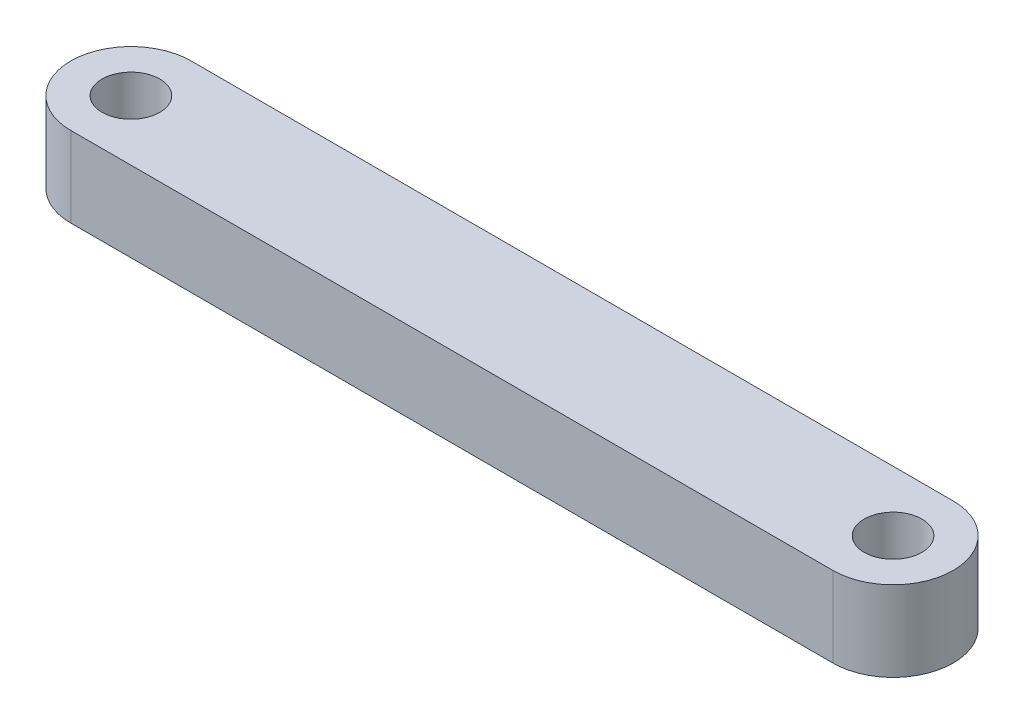
SolidWorks part; units mm, degrees
ref_plane "Front Plane" through (0, 0, 0) normal (0, 0, 1) x (1, 0, 0)
ref_plane "Top Plane" through (0, 0, 0) normal (0, 1, 0) x (1, 0, 0)
ref_plane "Right Plane" through (0, 0, 0) normal (1, 0, 0) x (0, 0, -1)
sketch "Sketch1" plane through (0, 0, 0) normal (0, 1, 0) x (1, 0, 0)
  line L0 (0, 0) -> (-60.325, 0) construction
  line L1 (0, -4.7625) -> (-60.325, -4.7625)
  line L2 (0, 4.7625) -> (-60.325, 4.7625)
  arc A0 (0, -4.7625) -> (0, 4.7625) centre (0, 0) ccw
  arc A1 (-60.325, 4.7625) -> (-60.325, -4.7625) centre (-60.325, 0) ccw
  circle A2 centre (-60.325, 0) radius 2.286
  circle A3 centre (0, 0) radius 2.286
  point P3 (-30.1625, 0)
  dimension "D1" = 4.572
  dimension "D2" = 4.7625
  dimension "D3" = 60.325
extrude "Boss-Extrude1" add sketch "Sketch1" along normal blind 6.35
